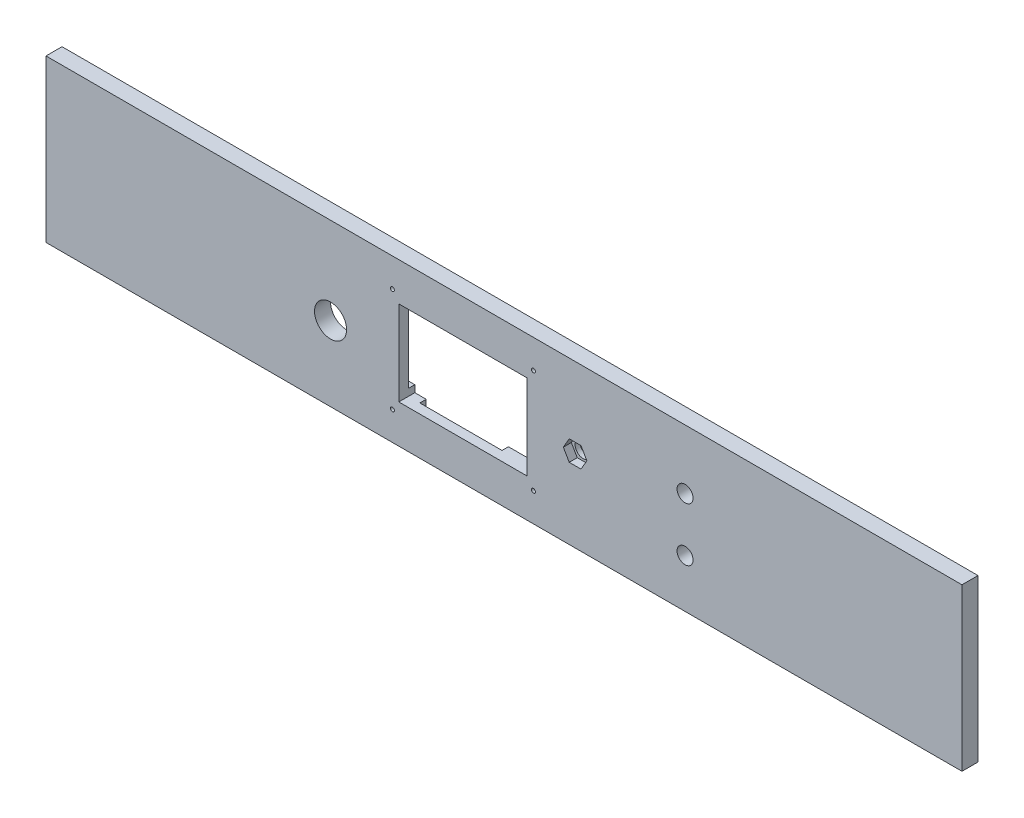
SolidWorks part; units mm, degrees
ref_plane "Front Plane" through (0, 0, 0) normal (0, 0, 1) x (1, 0, 0)
ref_plane "Top Plane" through (0, 0, 0) normal (0, 1, 0) x (1, 0, 0)
ref_plane "Right Plane" through (0, 0, 0) normal (1, 0, 0) x (0, 0, -1)
sketch "Sketch1" plane through (0, 0, 0) normal (0, 0, 1) x (1, 0, 0)
  line L1 (0, 0) -> (571.5, 0)
  line L2 (0, 0) -> (0, 100.8)
  line L3 (0, 100.8) -> (571.5, 100.8)
  line L4 (571.5, 0) -> (571.5, 100.8)
  dimension "D1" = 100.8
  dimension "D2" = 571.5
extrude "Boss-Extrude1" add sketch "Sketch1" along normal mid plane 10
sketch "Sketch2" plane through (0, 0, -5) normal (0, 0, -1) x (-1, 0, 0)
  line L0 (-298.6236, 24.9) -> (-221.6236, 24.9) construction
  line L1 (-300.1236, 23.9) -> (-220.1236, 23.9)
  line L2 (-300.1236, 23.9) -> (-300.1236, 76.9)
  line L3 (-300.1236, 76.9) -> (-220.1236, 76.9)
  line L4 (-220.1236, 23.9) -> (-220.1236, 76.9)
  line L5 (-299.1236, 75.4) -> (-299.1236, 25.4) construction
  line L6 (-221.6236, 75.9) -> (-298.6236, 75.9) construction
  line L7 (-221.1236, 25.4) -> (-221.1236, 75.4) construction
  dimension "D1" = 1
  dimension "D2" = 1
  dimension "D3" = 1
  dimension "D4" = 1
extrude "Cut-Extrude1" cut sketch "Sketch2" against normal through all
sketch "Sketch3" plane through (0, 0, -5) normal (0, 0, -1) x (-1, 0, 0)
  line L0 (-217.1434, 15.4) -> (-228.2236, 15.4) construction
  line L1 (-300.1236, 23.9) -> (-278.5236, 23.9)
  line L2 (-300.1236, 23.9) -> (-300.1236, 76.9)
  line L3 (-300.1236, 76.9) -> (-220.1236, 76.9)
  line L4 (-220.1236, 23.9) -> (-220.1236, 28.2292)
  line L6 (-278.5236, 23.9) -> (-278.5236, 15.4)
  line L7 (-278.5236, 15.4) -> (-227.2236, 15.4)
  line L8 (-227.2236, 23.9) -> (-227.2236, 15.4)
  line L9 (-213.6236, 81.8802) -> (-213.6236, 18.9198) construction
  line L10 (-220.1236, 28.2292) -> (-213.6236, 28.2292)
  line L12 (-220.1236, 72.5708) -> (-213.6236, 72.5708)
  line L13 (-213.6236, 28.2292) -> (-213.6236, 72.5708)
  line L14 (-222.2635, 71.5708) -> (-215.8236, 71.5708) construction
  line L15 (-215.8236, 29.2292) -> (-222.2635, 29.2292) construction
  line L16 (-228.2236, 15.4) -> (-228.2236, 17.15) construction
  line L17 (-277.5236, 15.4) -> (-277.5236, 17.15) construction
  line L18 (-227.2236, 23.9) -> (-220.1236, 23.9)
  line L19 (-220.1236, 72.5708) -> (-220.1236, 76.9)
  dimension "D1" = 1
  dimension "D2" = 1
  dimension "D3" = 1
  dimension "D4" = 1
extrude "Cut-Extrude2" cut sketch "Sketch3" against normal blind 4
sketch "Sketch4" plane through (0, 0, -5) normal (0, 0, -1) x (-1, 0, 0)
  line L3 (-571.5, 100.8) -> (0, 100.8) construction
  line L4 (-300.1236, 76.9) -> (-300.1236, 23.9) construction
  circle A0 centre (-330.1236, 50.8) radius 7.5
  dimension "D3" = 15
  dimension "D1" = 50
  dimension "D2" = 30
extrude "Cut-Extrude3" cut sketch "Sketch4" against normal blind 2
sketch "Sketch5" plane through (0, 0, -3) normal (0, 0, -1) x (-1, 0, 0)
  circle A0 centre (-330.1236, 50.8) radius 5
  dimension "D1" = 10
extrude "Cut-Extrude4" cut sketch "Sketch5" against normal through all
sketch "Sketch6" plane through (0, 0, 5) normal (0, 0, 1) x (1, 0, 0)
  line L1 (337.4675, 50.8) -> (333.7956, 57.16)
  line L2 (333.7956, 57.16) -> (326.4517, 57.16)
  line L3 (326.4517, 57.16) -> (322.7797, 50.8)
  line L4 (322.7797, 50.8) -> (326.4517, 44.44)
  line L5 (326.4517, 44.44) -> (333.7956, 44.44)
  line L6 (333.7956, 44.44) -> (337.4675, 50.8)
  circle A0 centre (330.1236, 50.8) radius 6.36 construction
  dimension "D1" = 12.72
extrude "Cut-Extrude5" cut sketch "Sketch6" against normal blind 5
sketch "Sketch7" plane through (0, 0, -5) normal (0, 0, -1) x (-1, 0, 0)
  point P0 (-304.1236, 82.9)
  point P1 (-304.1236, 17.9)
  point P3 (-216.1236, 17.9)
  point P5 (-216.1236, 82.9)
hole_wizard "Tap Drill for M3x0.5 Tap1" positions "Sketch7" profile "Sketch8" hole size "M3x0.5" standard "ANSI Metric" end condition through all
sketch "Sketch8" plane through (304.1236, 82.9, -5) normal (1, 0, 0) x (0, 1, 0)
  line L0 (0, 0) -> (0, 10)
  line L1 (0, 10) -> (1.25, 10)
  line L2 (1.25, 10) -> (1.25, 0)
  line L5 (1.25, 0) -> (0, 0)
  line L11 (0, -6.35) -> (0, 107.95) construction
  dimension "Thru Hole Dia." = 2.5
  dimension "Thru Hole Depth" = 10
sketch "Sketch9" plane through (0, 0, 5) normal (0, 0, 1) x (1, 0, 0)
  circle A0 centre (177.5367, 46.6) radius 10
  circle A1 centre (398.7408, 63.7028) radius 5
  circle A2 centre (398.7408, 30.252) radius 5
  dimension "D1" = 20
  dimension "D2" = 10
  dimension "D3" = 10
extrude "power and usb cables" cut sketch "Sketch9" against normal through all
